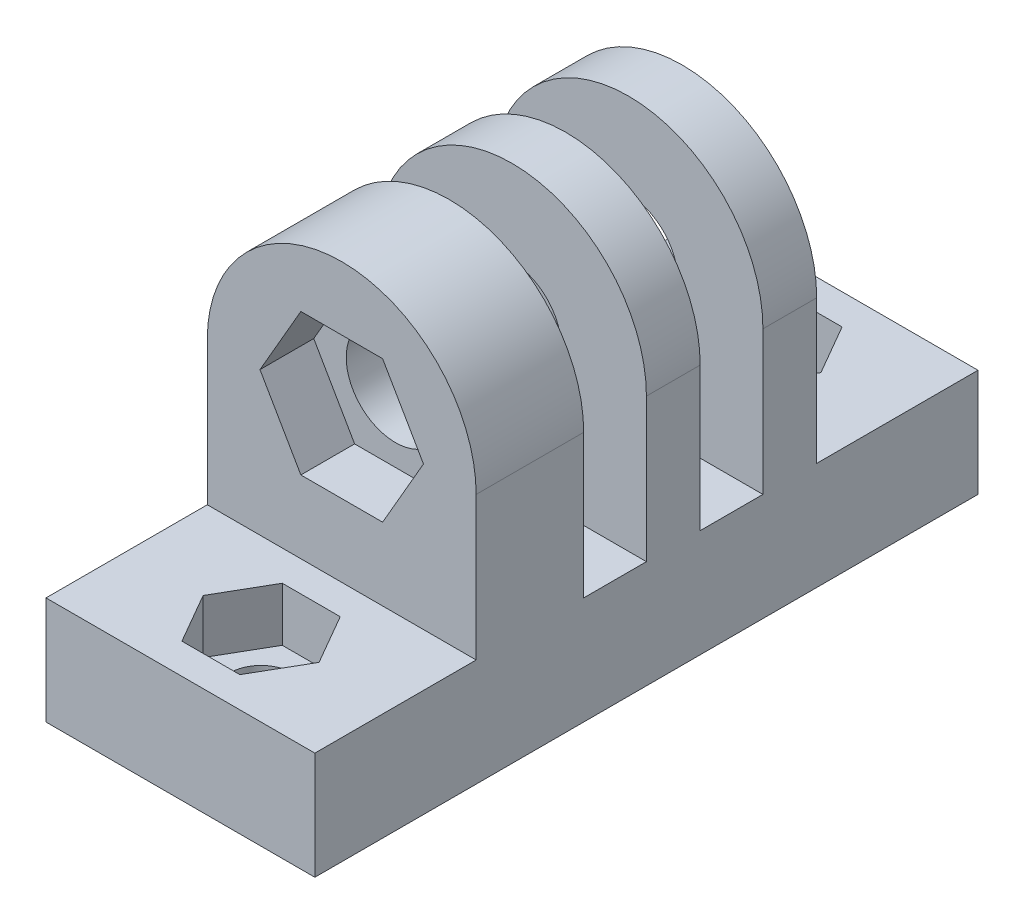
SolidWorks part; units mm, degrees
material "PET"
ref_plane "Plan de face" through (0, 0, 0) normal (0, 0, 1) x (1, 0, 0)
ref_plane "Plan de dessus" through (0, 0, 0) normal (0, 1, 0) x (1, 0, 0)
ref_plane "Plan de droite" through (0, 0, 0) normal (1, 0, 0) x (0, 0, -1)
sketch "Esquisse1" plane through (0, 0, 0) normal (0, 0, 1) x (1, 0, 0)
  line L1 (0, 0) -> (15, 0)
  line L2 (0, 0) -> (0, 8)
  line L3 (0, 8) -> (15, 8) construction
  line L4 (15, 0) -> (15, 8)
  arc A0 (15, 8) -> (0, 8) centre (7.5, 8) ccw
  circle A1 centre (7.5, 8) radius 2.75
  circle A2 centre (7.5, 8) radius 7.5 construction
  dimension "D2" = 5.5
  dimension "D1" = 15
  dimension "D3" = 8
extrude "Boss.-Extru.1" add sketch "Esquisse1" along normal blind 3
sketch "Esquisse2" plane through (0, 0, 0) normal (0, -1, 0) x (1, 0, 0)
  line L0 (15, 3) -> (15, 0) construction
  line L1 (0, 3) -> (15, 3)
  line L2 (0, 3) -> (0, -22)
  line L3 (0, -22) -> (15, -22)
  line L4 (15, 3) -> (15, -22)
  dimension "D1" = 25
extrude "Boss.-Extru.2" add sketch "Esquisse2" along normal blind 6
pattern_linear "Répétition linéaire1" count 3 spacing 6.5 along (0, 0, -1) of "Boss.-Extru.1"
sketch "Esquisse3" plane through (0, 0, 3) normal (0, 0, 1) x (1, 0, 0)
  line L1 (9.7805, 4.05) -> (12.0611, 8)
  line L2 (12.0611, 8) -> (9.7805, 11.95)
  line L3 (9.7805, 11.95) -> (5.2195, 11.95)
  line L4 (5.2195, 11.95) -> (2.9389, 8)
  line L5 (2.9389, 8) -> (5.2195, 4.05)
  line L6 (5.2195, 4.05) -> (9.7805, 4.05)
  line L9 (0, 8) -> (0, -6)
  line L10 (0, -6) -> (15, -6)
  line L11 (15, -6) -> (15, 8)
  line L12 (0, 8) -> (0, -6)
  line L13 (0, -6) -> (15, -6)
  line L14 (15, -6) -> (15, 8)
  circle A0 centre (7.5, 8) radius 3.95 construction
  arc A2 (15, 8) -> (0, 8) centre (7.5, 8) ccw
  arc A3 (15, 8) -> (0, 8) centre (7.5, 8) ccw
  dimension "D1" = 7.9
  dimension "D2" = 0
extrude "Boss.-Extru.3" add sketch "Esquisse3" along normal blind 3
sketch "Esquisse4" plane through (0, 0, 0) normal (0, 1, 0) x (1, 0, 0)
  line L0 (0, 22) -> (15, 13) construction
  line L2 (9.1166, 14.7) -> (10.7332, 17.5)
  line L3 (10.7332, 17.5) -> (9.1166, 20.3)
  line L4 (9.1166, 20.3) -> (5.8834, 20.3)
  line L5 (5.8834, 20.3) -> (4.2668, 17.5)
  line L6 (4.2668, 17.5) -> (5.8834, 14.7)
  line L7 (5.8834, 14.7) -> (9.1166, 14.7)
  circle A0 centre (7.5, 17.5) radius 2.8 construction
  circle A1 centre (7.5, 17.5) radius 1.75
  dimension "D2" = 3.5
  dimension "D1" = 5.6
extrude "Enlèv. mat.-Extru.1" cut sketch "Esquisse4" against normal blind 3 contours L2 L3 L4 L5 L6 L7
extrude "Enlèv. mat.-Extru.3" cut sketch "Esquisse4<3>" against normal through all contours A1 region at (7.5, 0, -17.5)
sketch "Esquisse4<3>" plane through (0, 0, 0) normal (0, 1, 0) x (1, 0, 0) same geometry as "Esquisse4"
ref_plane "Plan1" through (0, 0, -3.5) normal (0, 0, -1) x (-1, 0, 0)
mirror "Symétrie1" about plane through (0, 0, -3.5) normal (0, 0, -1) of "Boss.-Extru.2", "Enlèv. mat.-Extru.3", "Enlèv. mat.-Extru.1"
